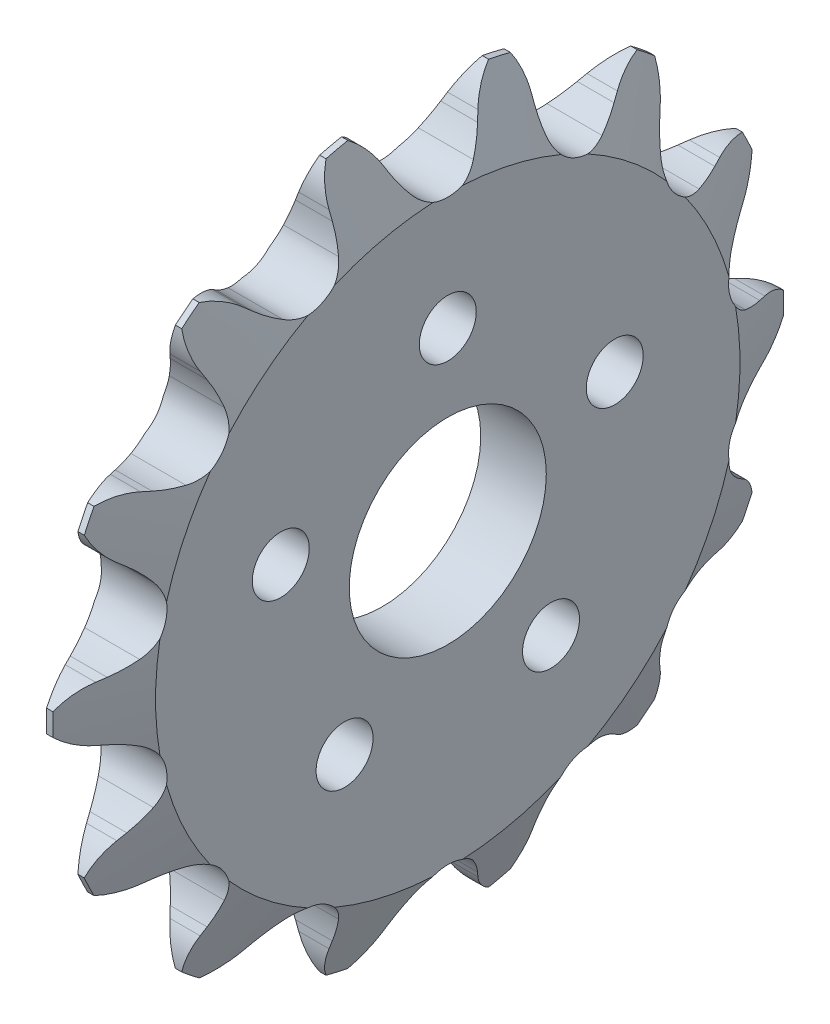
SolidWorks part; units mm, degrees
material "Alloy Steel"
ref_plane "Front Plane" through (0, 0, 0) normal (0, 0, 1) x (1, 0, 0)
ref_plane "Top Plane" through (0, 0, 0) normal (0, 1, 0) x (1, 0, 0)
ref_plane "Right Plane" through (0, 0, 0) normal (1, 0, 0) x (0, 0, -1)
ref_axis "X AXIS" through (-88.99, 0, 0) along (1, 0, 0)
ref_axis "Y AXIS" through (0, -55, 0) along (0, 1, 0)
ref_axis "Z AXIS" through (0, 0, 55) along (0, 0, -1)
other "Freeze***"
sketch "Sketch1" plane through (0, 0, 0) normal (1, 0, 0) x (0, 0, -1)
  line L0 (0, 21.4025) -> (-9.2862, 19.283) construction
  line L1 (-2.8717, 21.1333) -> (-3.1055, 21.6283)
  line L2 (-2.8717, 21.1333) -> (3.1455, 23.9758) construction
  line L3 (3.1455, 23.9758) -> (0, 21.4025) construction
  line L4 (0, 21.4025) -> (-2.9988, 21.4025) construction
  line L5 (-5.4268, 23.7765) -> (-4.6431, 20.3427) construction
  line L6 (0, 21.4025) -> (0, 18.8117) construction
  circle A0 centre (0, 0) radius 21.4025 construction
  arc A1 (-2.0053, 19.762) -> (0, 18.8117) centre (0, 21.4025) ccw
  arc A2 (-2.0053, 19.762) -> (-2.8717, 21.1333) centre (3.1455, 23.9758) cw
  arc A3 (-3.1055, 21.6283) -> (-5.4268, 23.7765) centre (-6.9337, 19.8199) ccw
sketch "Sketch2" plane through (0, 0, 0) normal (0, 0, 1) x (1, 0, 0)
  line L0 (0, 0) -> (0, 23.7837) construction
  line L1 (-0.2064, 23.7837) -> (0.2064, 23.7837)
  line L2 (0.2064, 23.7837) -> (2.1336, 19.0212)
  line L3 (2.1336, 19.0212) -> (2.1336, 0)
  line L4 (-2.1336, 0) -> (2.1336, 0)
  line L5 (-2.1336, 19.0212) -> (-2.1336, 0)
  line L6 (-0.2064, 23.7837) -> (-2.1336, 19.0212)
  dimension "D1" = 23.7837
  dimension "D2" = 4.2672
revolve "Revolve1" add sketch "Sketch2" angle 360 about L4
sketch "Sketch3" plane through (0, 0, 0) normal (1, 0, 0) x (0, 0, -1)
  line L0 (-2.8717, 21.1333) -> (-3.1055, 21.6283) construction
  line L1 (-2.8717, 21.1333) -> (-3.1055, 21.6283)
  line L2 (0, 18.8117) -> (0, 0) construction
  line L3 (2.8717, 21.1333) -> (3.1055, 21.6283)
  arc A0 (-3.1055, 21.6283) -> (-5.4268, 23.7765) centre (-6.9337, 19.8199) ccw construction
  arc A1 (-2.8717, 21.1333) -> (-2.0053, 19.762) centre (3.1455, 23.9758) ccw construction
  arc A2 (-2.0053, 19.762) -> (0, 18.8117) centre (0, 21.4025) ccw construction
  arc A3 (-3.1055, 21.6283) -> (-5.4268, 23.7765) centre (-6.9337, 19.8199) ccw
  arc A4 (-2.8717, 21.1333) -> (-2.0053, 19.762) centre (3.1455, 23.9758) ccw
  arc A5 (-2.0053, 19.762) -> (2.0053, 19.762) centre (0, 21.4025) ccw
  arc A6 (2.8717, 21.1333) -> (2.0053, 19.762) centre (-3.1455, 23.9758) cw
  arc A7 (3.1055, 21.6283) -> (5.4268, 23.7765) centre (6.9337, 19.8199) cw
  arc A8 (-5.4268, 23.7765) -> (5.4268, 23.7765) centre (0, 0) cw
extrude "Cut-Extrude1" cut sketch "Sketch3" against normal through all both and the other way through all contours A8 A3 L1 A4 A5 A6 L3 A7 region at (0, 22.1043, 0)
pattern_circular "CirPattern1" count 14 over 360 about axis through (-88.99, 0, 0) along (1, 0, 0) of "Cut-Extrude1"
sketch "Sketch4" plane through (2.1336, 0, 0) normal (1, 0, 0) x (0, 0, -1)
  line L0 (0, 0) -> (0, 11.43) construction
  circle A0 centre (0, 0) radius 6.4135
  circle A1 centre (0, 11.43) radius 1.8542
  circle A2 centre (10.8706, 3.5321) radius 1.8542
  circle A3 centre (6.7184, -9.2471) radius 1.8542
  circle A4 centre (-6.7184, -9.2471) radius 1.8542
  circle A5 centre (-10.8706, 3.5321) radius 1.8542
  point P15 (0, 0)
  dimension "D1" = 12.827
  dimension "D2" = 5
  dimension "D3" = 3.7084
  dimension "D4" = 11.43
extrude "Cut-Extrude2" cut sketch "Sketch4" against normal through all
equation "\"p\"= 3 / 8"
equation "\"n\" = 14"
equation "\"Dr\"= 0.2"
equation "\"Ds\"= 1.005 * \"Dr\" + 0.003"
equation "\"PD\"= \"p\" * cosec ( 180 / \"n\" )"
equation "\"A\"= 35 + 60 / \"n\""
equation "\"B\"= 18 - 56 / \"n\""
equation "\"ac\"= 0.8 * \"Dr\""
equation "\"ab\"= 1.4 * \"Dr\""
equation "\"D1@Sketch1\"=\"PD\""
equation "\"D2@Sketch1\"=\"p\""
equation "\"D3@Sketch1\"=\"Ds\""
equation "\"D4@Sketch1\"=\"A\""
equation "\"D5@Sketch1\"=\"B\""
equation "\"D6@Sketch1\"=\"ac\""
equation "\"D7@Sketch1\"=\"ab\""
equation "\"D1@Sketch2\"=(\"PD\"+\"p\"/2)/2"
equation "\"D4@Sketch2\"=\"p\"/2"
equation "\"D1@CirPattern1\"=\"n\""
